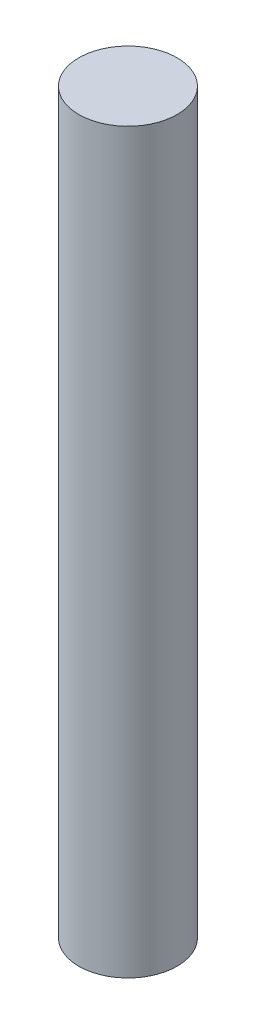
SolidWorks part; units mm, degrees
material "1023 Carbon Steel Sheet (SS)"
ref_plane "Front Plane" through (0, 0, 0) normal (0, 0, 1) x (1, 0, 0)
ref_plane "Top Plane" through (0, 0, 0) normal (0, 1, 0) x (1, 0, 0)
ref_plane "Right Plane" through (0, 0, 0) normal (1, 0, 0) x (0, 0, -1)
sketch "Sketch1" plane through (0, 0, 0) normal (1, 0, 0) x (0, 0, -1)
  line L0 (-2.925, 0) -> (-2.925, 13.5)
  line L1 (-1.425, 15) -> (1.425, 15)
  line L2 (2.925, 13.5) -> (2.925, 0)
  line L3 (-2.925, 0) -> (0, 0) construction
  line L4 (0, 0) -> (2.925, 0) construction
  arc A0 (1.425, 15) -> (2.925, 13.5) centre (1.425, 13.5) cw
  arc A1 (-2.925, 13.5) -> (-1.425, 15) centre (-1.425, 13.5) cw
  dimension "D1" = 1.5
  dimension "D2" = 15
  dimension "D3" = 5.85
sketch "Sketch2" plane through (0, 0, 0) normal (0, 1, 0) x (1, 0, 0)
  circle A0 centre (0, -2.925) radius 1
  dimension "D1" = 2
sweep "Sweep1" [suppressed] add profiles "Sketch2" path "Sketch1"
extrude "Boss-Extrude1" add sketch "Sketch2<2>" along normal blind 15
sketch "Sketch2<2>" plane through (0, 0, 0) normal (0, 1, 0) x (1, 0, 0) same geometry as "Sketch2"
